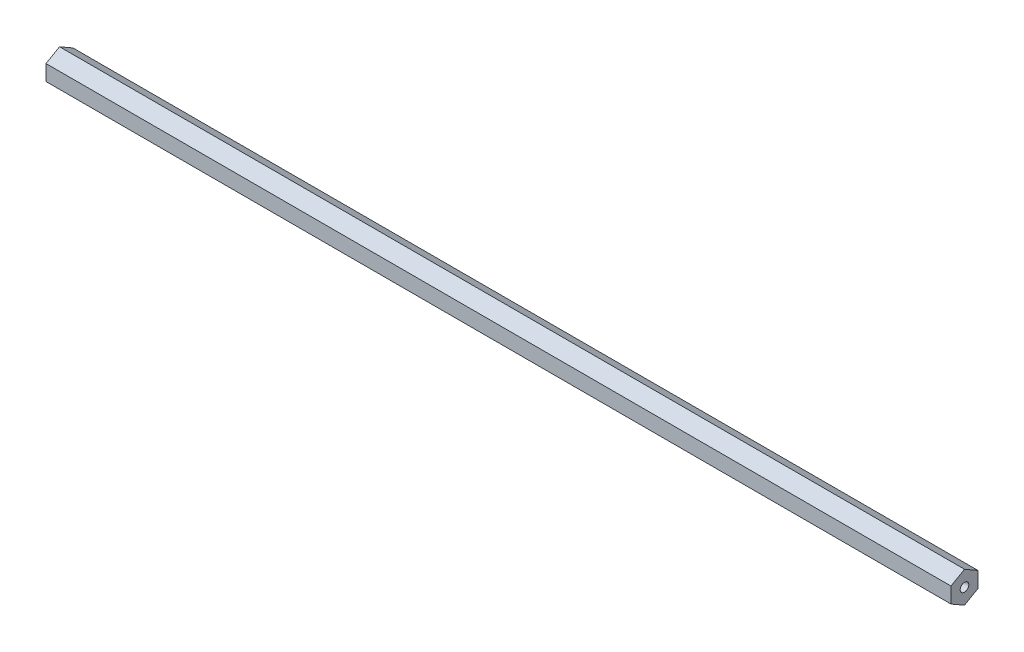
SolidWorks part; units mm, degrees
material "7075-T6 (SN)"
ref_plane "Front Plane" through (0, 0, 0) normal (0, 0, 1) x (1, 0, 0)
ref_plane "Top Plane" through (0, 0, 0) normal (0, 1, 0) x (1, 0, 0)
ref_plane "Right Plane" through (0, 0, 0) normal (1, 0, 0) x (0, 0, -1)
sketch "Sketch1" plane through (0, 0, 0) normal (1, 0, 0) x (0, 0, -1)
  line L1 (0, 7.3323) -> (-6.35, 3.6662)
  line L2 (-6.35, 3.6662) -> (-6.35, -3.6662)
  line L3 (-6.35, -3.6662) -> (0, -7.3323)
  line L4 (0, -7.3323) -> (6.35, -3.6662)
  line L5 (6.35, -3.6662) -> (6.35, 3.6662)
  line L6 (6.35, 3.6662) -> (0, 7.3323)
  circle A2 centre (0, 0) radius 6.35 construction
  dimension "D2" = 12.7
extrude "Boss-Extrude1" add sketch "Sketch1" along normal mid plane 425.45 contours L5 L6 L1 L2 L3 L4 region at (0, 0, 0)
sketch "Sketch3" plane through (-200.025, 0, 0) normal (-1, 0, 0) x (0, 0, 1)
  circle A0 centre (0, 0) radius 6.35
  dimension "D1" = 12.7
hole_wizard "#10-32 Tapped Hole1" positions "3DSketch1" profile "Sketch4" tap size "#10-32" standard "ANSI Inch"
sketch3d "3DSketch1"
  point P10 (212.725, 0, 0)
  point P13 (-212.725, 0, 0)
sketch "Sketch4" plane through (212.725, 0, 0) normal (0, 1, 0) x (0, 0, -1)
  line L0 (0, 0) -> (0, 17.5608)
  line L1 (0, 17.5608) -> (2.0193, 16.3474)
  line L2 (2.0193, 16.3474) -> (2.0193, 0)
  line L5 (2.0193, 0) -> (0, 0)
  line L10 (0, 17.5608) -> (-2.0193, 16.3474) construction
  line L11 (0, -6.35) -> (0, 107.95) construction
  dimension "Tap Drill Dia." = 4.0386
  dimension "Tap Drill Depth" = 16.3474
  dimension "Drill Angle" = 118
cosmetic thread "Hole Thread1" parameters "D1"=13.97, "D2"=4.826
cosmetic thread "Hole Thread2" parameters "D1"=13.97, "D2"=4.826
